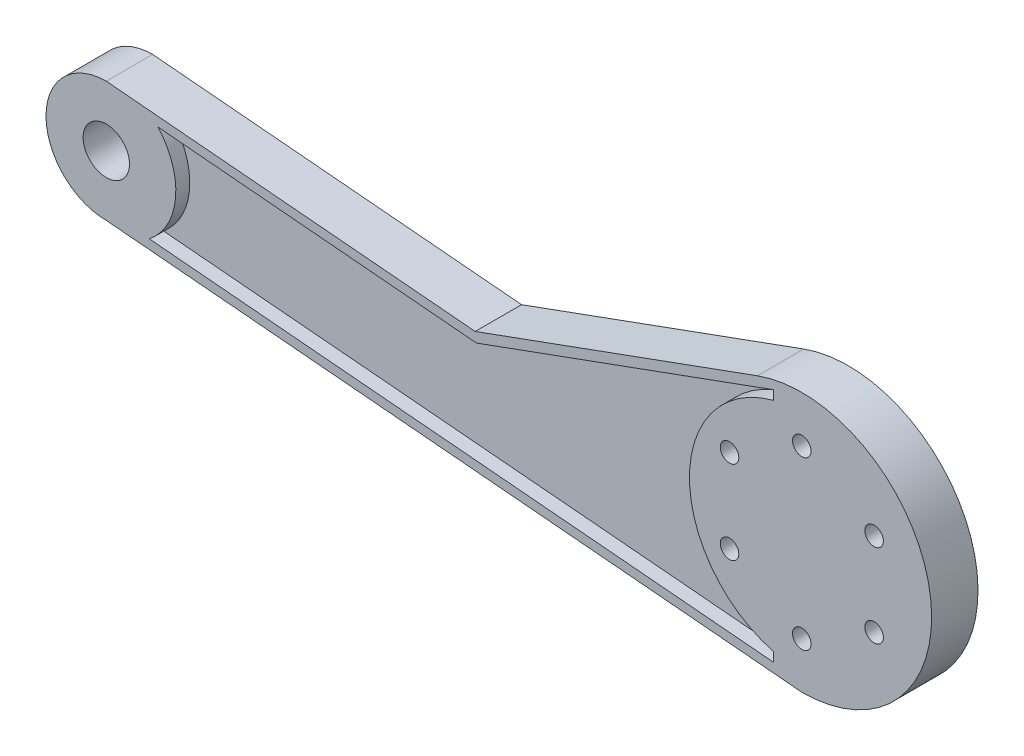
SolidWorks part; units mm, degrees
ref_plane "Front Plane" through (0, 0, 0) normal (1, 0, 0) x (0, 1, 0)
ref_plane "Top Plane" through (0, 0, 0) normal (0, 0, 1) x (0, 1, 0)
ref_plane "Right Plane" through (0, 0, 0) normal (0, 1, 0) x (-1, 0, 0)
sketch "Sketch1" plane through (0, 0, 0) normal (0, 0, 1) x (-1, 0, 0)
  line L16 (149.9882, -11.1223) -> (70.4316, -4.162)
  line L25 (0, 28) -> (149.9882, 14.8777)
  line L26 (9.5766, -26.3114) -> (70.4316, -4.162)
  circle A13 centre (149.9882, 1.8777) radius 13 construction
  arc A14 (0, 28) -> (9.5766, -26.3114) centre (0, 0) ccw
  circle A15 centre (0, 0) radius 18 construction
  arc A20 (149.9882, 14.8777) -> (149.9882, -11.1223) centre (149.9882, 1.8777) cw
  circle A21 centre (149.9882, 1.8777) radius 5
  dimension "D4" = 36
  dimension "D2" = 10
  dimension "D3" = 150
  dimension "D10" = 10
  dimension "D6" = 5
  dimension "D5" = 8
  dimension "D7" = 20
extrude "Boss-Extrude1" add sketch "Sketch1" along normal blind 10
ref_plane "Plane1" through (0, 0, 5) normal (0, 0, 1) x (1, 0, 0)
sketch "Sketch3" plane through (0, 0, 10) normal (0, 0, 1) x (1, 0, 0)
  line L0 (-140.7305, -13.68) -> (-6.0628, -25.4619)
  line L1 (-138.8217, 8.1377) -> (-70.1642, 2.1309)
  line L2 (-70.1642, 2.1309) -> (-6.0628, 25.4619)
  line L3 (-6.0628, 25.4619) -> (-6.0628, 23.4619)
  line L4 (-6.0628, -25.4619) -> (-6.0628, -23.4619)
  line L5 (-9.5766, 26.3114) -> (-70.4316, 4.162) construction
  line L6 (-70.4316, 4.162) -> (-149.9882, 11.1223) construction
  line L7 (-149.9882, -14.8777) -> (0, -28) construction
  arc A3 (-6.0628, -23.4619) -> (-6.0628, 23.4619) centre (0, 0) cw
  arc A4 (0, -28) -> (-9.5766, 26.3114) centre (0, 0) ccw construction
  arc A5 (-138.8217, 8.1377) -> (-140.7305, -13.68) centre (-149.9882, -1.8777) cw
  circle A6 centre (-149.9882, -1.8777) radius 5 construction
  dimension "D1" = 2
  dimension "D5" = 10
  dimension "D2" = 2
  dimension "D3" = 2
  dimension "D4" = 2
extrude "Cut-Extrude2" cut sketch "Sketch3" against normal blind 3 contours L1 A5 L0 L4 A3 L3 L2
sketch "Sketch4" plane through (0, 0, 10) normal (0, 0, 1) x (1, 0, 0)
  circle A0 centre (0, 0) radius 18 construction
  arc A1 (0, -28) -> (-9.5766, 26.3114) centre (0, 0) ccw construction
  circle A2 centre (0, 18) radius 2
  circle A3 centre (15.5885, 9) radius 2
  circle A4 centre (15.5885, -9) radius 2
  circle A5 centre (0, -18) radius 2
  circle A6 centre (-15.5885, -9) radius 2
  circle A7 centre (-15.5885, 9) radius 2
  dimension "D1" = 36
  dimension "D2" = 4
  dimension "D3" = 6
extrude "Cut-Extrude3" cut sketch "Sketch4" against normal through all
equation "\"ThighLength\"= 150"
equation "\"BearingBore\"=10"
equation "\"MinShinWidth\"= 20"
equation "\"HipBore\"=27"
equation "\"ShinThickness\"=10"
equation "\"ThighThickness\"=10"
equation "\"D1@Boss-Extrude1\"= \"ThighThickness\""
equation "\"MaxBending\"=135"
equation "\"KneeLength\" =80"
equation "\"ThighJointDistance\"=157.485"
equation "\"D3@Sketch1\"=\"ThighLength\""
